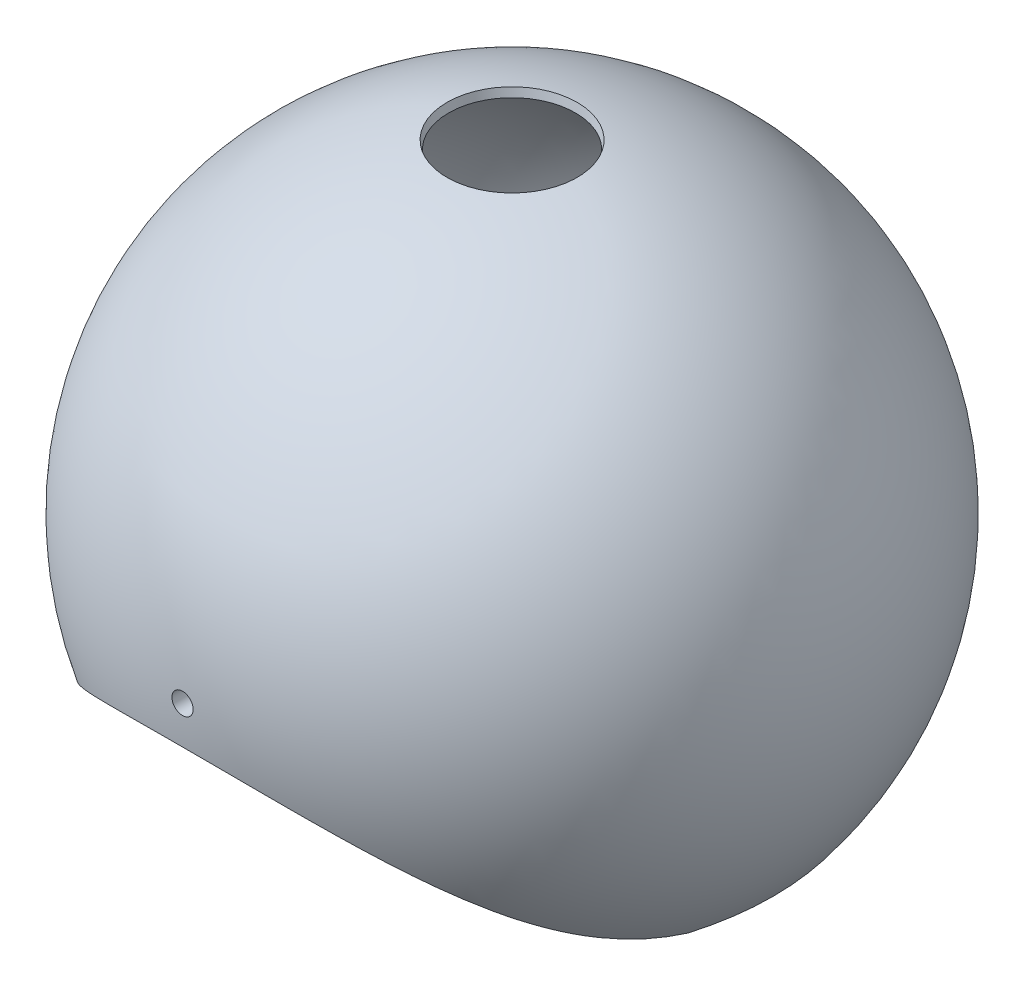
SolidWorks part; units mm, degrees
ref_plane "Front Plane" through (0, 0, 0) normal (0, 0, 1) x (1, 0, 0)
ref_plane "Top Plane" through (0, 0, 0) normal (0, 1, 0) x (1, 0, 0)
ref_plane "Right Plane" through (0, 0, 0) normal (1, 0, 0) x (0, 0, -1)
sketch "Sketch1" plane through (0, 0, 0) normal (0, 0, 1) x (1, 0, 0)
  line L0 (0, 0) -> (0, 78) construction
  line L1 (-61.7509, -47.6532) -> (-59.2045, -47.6532)
  line L3 (-15.3947, 76.4657) -> (-15, 74.505)
  arc A0 (-15.3947, 76.4657) -> (-61.7509, -47.6532) centre (0, 0) ccw
  arc A1 (-15, 74.505) -> (-59.2045, -47.6532) centre (0, 0) ccw
  point P7 (0, 0)
  point P8 (0, 0)
  point P9 (0, 0)
  point P10 (0, 0)
  point P11 (-64.5431, -40.1272)
  point P12 (-66.2048, -41.2422)
  point P13 (-59.2045, -47.6532)
  point P14 (-60.7614, -48.9086)
  point P15 (-61.7609, -47.6532)
  dimension "D1" = 78
  dimension "D2" = 2
  dimension "D3" = 15
revolve "Revolve1" add sketch "Sketch1" angle 360 about L0
ref_plane "Plane1" through (0, 0, 77) normal (0, 0, 1) x (1, 0, 0)
sketch "Sketch2" plane through (0, 0, 77) normal (0, 0, 1) x (1, 0, 0)
  circle A0 centre (0, 0) radius 5
  dimension "D1" = 10
extrude "Boss-Extrude1" add sketch "Sketch2" against normal blind 10 contours A0
ref_plane "Plane3" through (0, 0, -78) normal (0, 0, 1) x (1, 0, 0)
sketch "Sketch3" plane through (0, 0, 0) normal (0, 0, 1) x (1, 0, 0)
  line L0 (-30.219, 60.8224) -> (-30.219, 70.8224)
  line L1 (-30.219, 60.8224) -> (-47.219, 60.8224)
  arc A0 (-30.219, 70.8224) -> (-47.219, 60.8224) centre (0, 0) ccw
  point P5 (40.819, 0)
  point P6 (40.819, 0)
  point P7 (0, 0)
  point P8 (0, 0)
  point P9 (0, 0)
  dimension "D1" = 77
  dimension "D2" = 10
  dimension "D3" = 17
ref_axis "Axis1" through (0, 76.4657, 0) along (0, -1, 0)
revolve "Revolve2" add sketch "Sketch3" angle 360 about axis through (0, 76.4657, 0) along (0, -1, 0)
sketch "Sketch4" plane through (0, 60.8224, 0) normal (0, -1, 0) x (1, 0, 0)
  line L2 (19.275, 30.7) -> (-19.275, 30.7)
  line L4 (19.275, 23.2737) -> (-19.275, 23.2737)
  circle A0 centre (0, 0) radius 30.219 construction
  circle A1 centre (3.2, 34.1) radius 1.4
  circle A2 centre (-3.2, 34.1) radius 1.4
  arc A3 (19.275, 30.7) -> (-19.275, 30.7) centre (0, 0) cw
  arc A4 (19.275, 23.2737) -> (-19.275, 23.2737) centre (0, 0) cw
  point P7 (-19.275, 23.2737)
  point P8 (19.275, 23.2737)
  point P15 (19.275, -30.7)
  point P16 (0, 0)
  point P17 (-19.275, -23.2737)
  dimension "D1" = 2.8
  dimension "D2" = 2.8
extrude "Cut-Extrude1" cut sketch "Sketch4" against normal blind 5
mirror "Mirror1" about plane through (0, 0, 0) normal (0, 0, 1) of "Boss-Extrude1"
sketch "Sketch5" plane through (0, 0, 67) normal (0, 0, -1) x (-1, 0, 0)
  circle A0 centre (0, 0) radius 2.45
  dimension "D1" = 4.9
extrude "Cut-Extrude2" cut sketch "Sketch5" against normal blind 3
ref_plane "Plane4" through (0, 0, 72) normal (0, 0, -1) x (-1, 0, 0)
sketch "Sketch6" plane through (0, 0, 72) normal (0, 0, -1) x (-1, 0, 0)
  circle A0 centre (0, 0) radius 2.5
  dimension "D1" = 5
sketch "Sketch7" plane through (0, 0, 70) normal (0, 0, -1) x (-1, 0, 0)
  circle A0 centre (0, 0) radius 1
  dimension "D1" = 2
extrude "Cut-Extrude3" cut sketch "Sketch6" against normal blind 13
extrude "Cut-Extrude4" cut sketch "Sketch7" against normal blind 13
sketch "Sketch8" plane through (0, 0, 77) normal (0, 0, 1) x (1, 0, 0)
  line L0 (59.2045, -47.6532) -> (-59.2045, -47.6532)
  arc A0 (59.2045, -47.6532) -> (-59.2045, -47.6532) centre (0, -74.4828) ccw
  point P3 (0, 0)
  point P6 (0, 0)
  point P7 (0, 0)
  point P9 (0, 0)
  point P10 (0, 0)
  dimension "D1" = 65
extrude "Cut-Extrude5" cut sketch "Sketch8" against normal through all and the other way through all contours A0 L0
